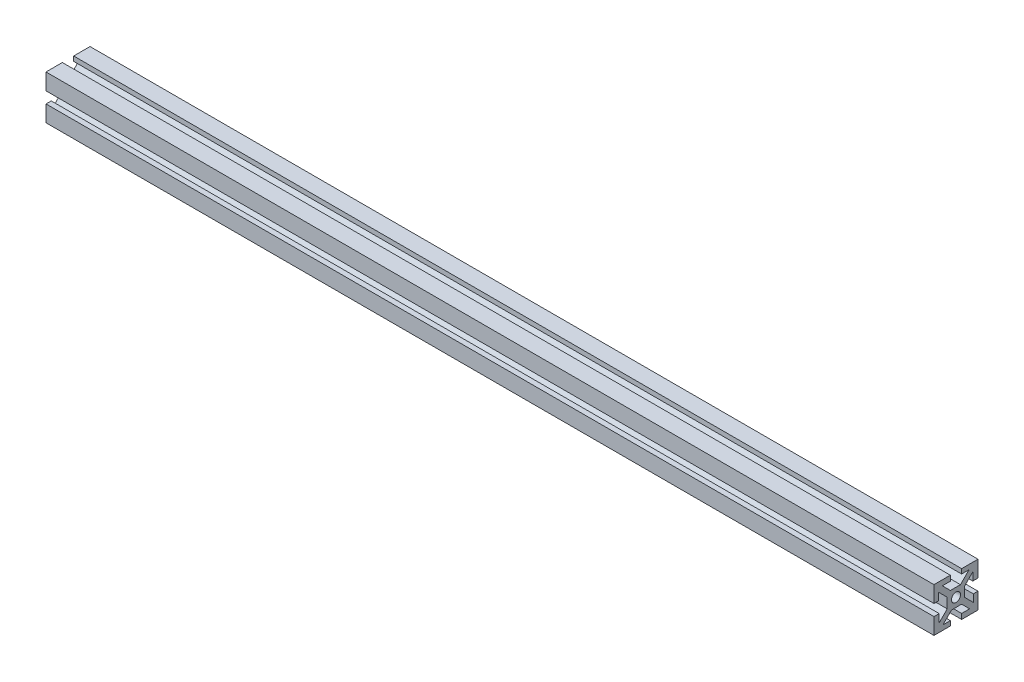
SolidWorks part; units mm, degrees
ref_plane "Front Plane" through (0, 0, 0) normal (0, 0, 1) x (1, 0, 0)
ref_plane "Top Plane" through (0, 0, 0) normal (0, 1, 0) x (1, 0, 0)
ref_plane "Right Plane" through (0, 0, 0) normal (1, 0, 0) x (0, 0, -1)
sketch "Sketch1" plane through (0, 0, 0) normal (1, 0, 0) x (0, 0, -1)
  line L0 (2.5534, 5) -> (7.4749, 9.9215)
  line L1 (-5, 5) -> (5, 5)
  line L2 (-5, 5) -> (-5, -5)
  line L3 (-5, -5) -> (5, -5)
  line L4 (5, 5) -> (5, -5)
  line L5 (-5, 5) -> (5, -5) construction
  line L6 (-5, -5) -> (5, 5) construction
  line L7 (7.4749, 9.9215) -> (9.5962, 7.8001)
  line L8 (9.5962, 7.8001) -> (5, 3.2039)
  line L9 (5, 5) -> (13.6489, 13.6489) construction
  line L10 (7.4749, 9.9215) -> (3.24, 9.9215)
  line L11 (3.24, 9.9215) -> (3.24, 12.5962)
  line L12 (3.24, 12.5962) -> (12.5962, 12.5962)
  line L13 (9.5962, 7.8001) -> (9.5962, 3.24)
  line L14 (9.5962, 3.24) -> (12.5962, 3.24)
  line L15 (12.5962, 3.24) -> (12.5962, 12.5962)
  line L17 (0, 0) -> (0, 24.089) construction
  line L18 (0, 0) -> (23.75, 0) construction
  circle A0 centre (0, 0) radius 2.605
  point P0 (0, 0)
  dimension "D1" = 5.21
  dimension "D2" = 10
  dimension "D3" = 10
  dimension "D4" = 3
  dimension "D5" = 1.27
  dimension "D6" = 6.5
  dimension "D7" = 3.24
  dimension "D8" = 3.24
  dimension "D9" = 3
extrude "Boss-Extrude1" add sketch "Sketch1" along normal blind 508 contours L4 L1 L2 L3 A0 | L8 L7 L0 L1 L4 | L14 L15 L12 L11 L10 L7 L13 region at (0, 4.8586, -3.7767) region at (0, 6.7479, -6.3823) region at (0, 9.18, -9.3105)
ref_axis "Axis1" through (0, 0, 0) along (1, 0, 0)
pattern_circular "CirPattern1" count 4 over 360 about axis through (0, 0, 0) along (1, 0, 0) of "Boss-Extrude1"
